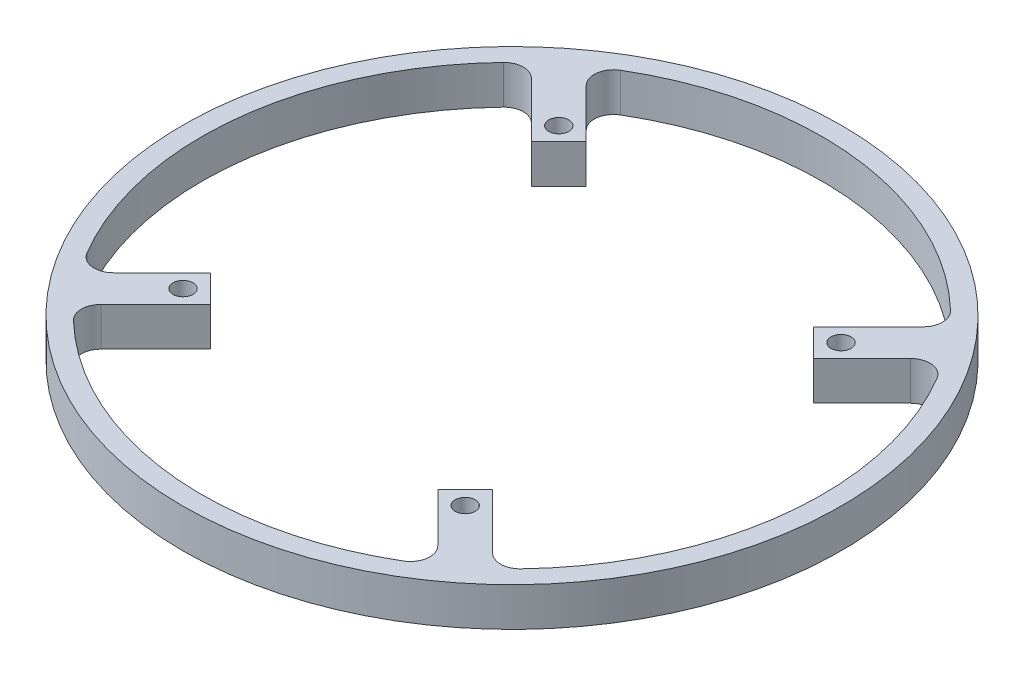
SolidWorks part; units mm, degrees
material "6061-T6 (SS)"
ref_plane "Front Plane" through (0, 0, 0) normal (0, 0, 1) x (1, 0, 0)
ref_plane "Top Plane" through (0, 0, 0) normal (0, 1, 0) x (1, 0, 0)
ref_plane "Right Plane" through (0, 0, 0) normal (1, 0, 0) x (0, 0, -1)
sketch "Sketch2" plane through (0, 0, 0) normal (1, 0, 0) x (0, 0, -1)
  line L0 (-55, 0) -> (-84.9998, 0)
  line L1 (-84.9998, 0) -> (-84.9998, 10)
  line L2 (-84.9998, 10) -> (-55, 10)
  line L5 (-55, 10) -> (-55, 0)
  dimension "D1" = 84.9998
  dimension "D2" = 10
  dimension "D3" = 55
ref_axis "Axis1" through (0, 3.6789, 0) along (0, 1, 0)
revolve "Revolve1" add sketch "Sketch2" angle 360 about axis through (0, 3.6789, 0) along (0, 1, 0)
sketch "Sketch9" plane through (0, 0, 0) normal (0, 1, 0) x (1, 0, 0)
  line L1 (42.4264, -42.4264) -> (-42.4264, -42.4264) construction
  line L2 (42.4264, -42.4264) -> (42.4264, 42.4264) construction
  line L3 (42.4264, 42.4264) -> (-42.4264, 42.4264) construction
  line L4 (-42.4264, -42.4264) -> (-42.4264, 42.4264) construction
  line L5 (0, 0) -> (0, 27.9091) construction
  line L7 (0, 0) -> (26.5726, 0) construction
  line L11 (-43.4619, 48.4619) -> (-36.3909, 55.533) construction
  line L12 (-43.4619, 48.4619) -> (-36.3909, 41.3909) construction
  line L13 (-36.3909, 55.533) -> (-29.3198, 48.4619) construction
  line L16 (-36.3909, 41.3909) -> (-36.3909, 55.533) construction
  line L18 (-43.4619, 48.4619) -> (-29.3198, 48.4619) construction
  line L20 (-29.3198, 48.4619) -> (-36.3909, 41.3909) construction
  point P3 (-42.4264, 42.4264)
  point P355 (-36.3909, 48.4619)
  dimension "D1" = 1.0355
  dimension "D2" = 60
  dimension "D3" = 6.0355
  dimension "D4" = 6.1237
hole_wizard "#6 (0.204) Diameter Hole1" positions "Sketch12" profile "Sketch13" hole size "#6" standard "ANSI Inch" end condition through all
sketch "Sketch12" plane through (0, 0, 0) normal (0, -1, 0) x (-1, 0, 0)
  point P0 (36.3909, 48.4619)
sketch "Sketch13" plane through (-36.3909, 0, -48.4619) normal (1, 0, 0) x (0, 0, -1)
  line L0 (0, 0) -> (0, 10)
  line L1 (0, 10) -> (2.5908, 10)
  line L2 (2.5908, 10) -> (2.5908, 0)
  line L5 (2.5908, 0) -> (0, 0)
  line L11 (0, -6.35) -> (0, 107.95) construction
  dimension "Thru Hole Dia." = 5.1816
  dimension "Thru Hole Depth" = 10
sketch "Sketch14" plane through (0, 0, 0) normal (0, -1, 0) x (1, 0, 0)
  line L0 (0, 0) -> (-36.3909, -48.4619) construction
  line L1 (-33.0708, -38.0708) -> (-54.0132, -59.0132)
  line L2 (-65.3239, 46.1818) -> (-55.533, 36.3909)
  line L3 (0, 0) -> (-48.4619, 36.3909) construction
  line L4 (-43.4619, -48.4619) -> (-36.3909, -41.3909) construction
  line L5 (-55.533, 36.3909) -> (-48.4619, 29.3198)
  line L6 (-41.3909, 36.3909) -> (-48.4619, 29.3198) construction
  line L7 (-41.3909, 36.3909) -> (-48.4619, 43.4619) construction
  line L8 (-48.4619, 43.4619) -> (-55.533, 36.3909) construction
  line L9 (-48.4619, 29.3198) -> (-55.533, 36.3909) construction
  line L10 (-41.3909, 36.3909) -> (-55.533, 36.3909) construction
  line L11 (-48.4619, 43.4619) -> (-48.4619, 29.3198) construction
  line L12 (-48.4619, 29.3198) -> (-41.3909, 36.3909)
  line L13 (-43.4619, -48.4619) -> (-36.3909, -55.533) construction
  line L14 (0, 0) -> (26.5726, 0) construction
  line L15 (-41.3909, 36.3909) -> (-38.0708, 33.0708)
  arc A0 (-33.0708, -38.0708) -> (-38.0708, 33.0708) centre (0, 0) cw
  arc A1 (-65.3239, 46.1818) -> (-54.0132, -59.0132) centre (0, 0) ccw
  circle A2 centre (0, 0) radius 84.9998 construction
  point P14 (-48.4619, 36.3909)
  dimension "D2" = 5
  dimension "D3" = 50.4288
extrude "Cut-Extrude1" cut sketch "Sketch14" against normal through all
pattern_circular "CirPattern1" count 4 over 360 about axis through (0, 3.6789, 0) along (0, 1, 0) of "Cut-Extrude1", "#6 (0.204) Diameter Hole1"
fillet "Fillet1" radius 5 8 edges at (54.0132, 5, 59.0132) (-54.0132, 5, -59.0132) (59.0132, 5, -54.0132) (-59.0132, 5, 54.0132) (46.1818, 5, 65.3239) (65.3239, 5, -46.1818) (-46.1818, 5, -65.3239) (-65.3239, 5, 46.1818)
equation "\"TubeDiameter\" = 6.6929in"
equation "\"D1@Sketch2\"=\"TubeDiameter\"/2"
